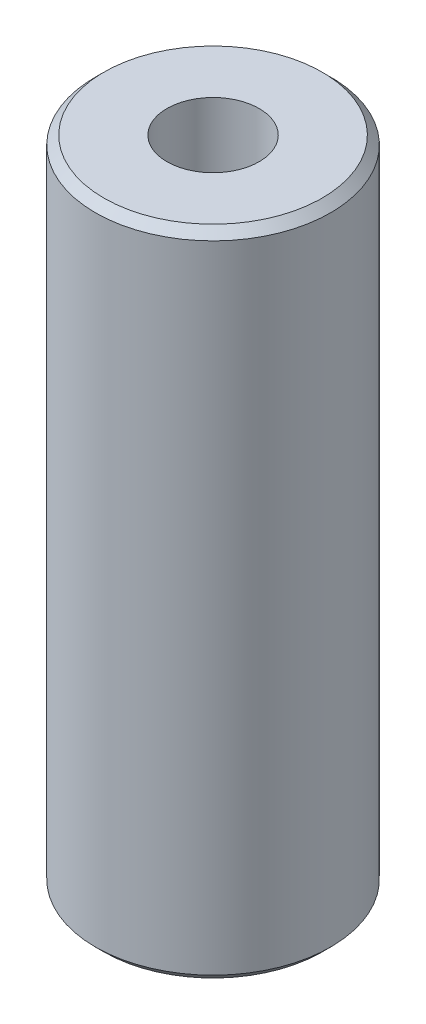
SolidWorks part; units mm, degrees
ref_plane "Front Plane" through (0, 0, 0) normal (0, 0, 1) x (1, 0, 0)
ref_plane "Top Plane" through (0, 0, 0) normal (0, 1, 0) x (1, 0, 0)
ref_plane "Right Plane" through (0, 0, 0) normal (1, 0, 0) x (0, 0, -1)
sketch "Sketch1" plane through (0, 0, 0) normal (0, 1, 0) x (1, 0, 0)
  circle A0 centre (0, 0) radius 37.5
  dimension "SHAFT_OD" = 75
extrude "Boss-Extrude1" add sketch "Sketch1" along normal blind 208.1585
sketch "Sketch2" plane through (0, 0, 0) normal (0, 1, 0) x (1, 0, 0)
  circle A0 centre (0, 0) radius 14.7057
  dimension "BORE_D" = 29.4115
extrude "Cut-Extrude1" cut sketch "Sketch2" along normal through all
chamfer "Chamfer1" distance 2.7001 angle 45 2 edges at (0, 208.1585, 37.5) (0, 0, 37.5)
